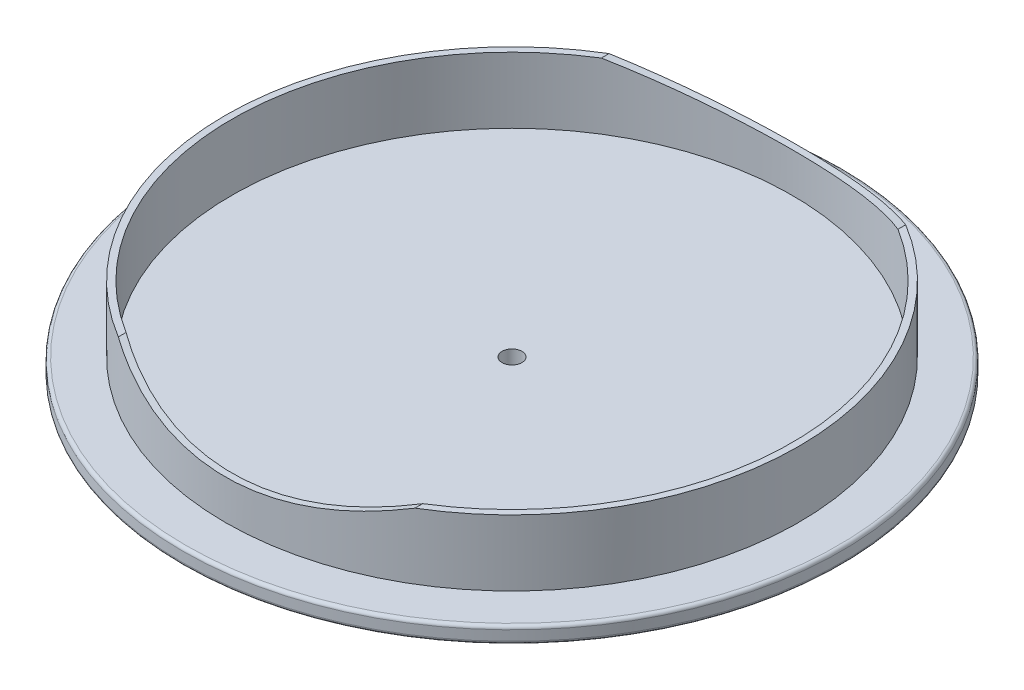
SolidWorks part; units mm, degrees
ref_plane "Front Plane" through (0, 0, 0) normal (0, 0, 1) x (1, 0, 0)
ref_plane "Top Plane" through (0, 0, 0) normal (0, 1, 0) x (1, 0, 0)
ref_plane "Right Plane" through (0, 0, 0) normal (1, 0, 0) x (0, 0, -1)
sketch "Sketch2" plane through (0, 0, 0) normal (0, 1, 0) x (1, 0, 0)
  circle A0 centre (0, 0) radius 100
  circle A3 centre (0, 0) radius 87
  circle A4 centre (0, 0) radius 85
  dimension "D1" = 170
  dimension "D2" = 174
  dimension "D3" = 200
extrude "Boss-Extrude1" add sketch "Sketch2" along normal blind 5 contours A0 A3 | A3 A4 | A4 region at (-97.1716, 0, 0) region at (-86.7539, 0, 0) region at (0, 0, 0)
extrude "Boss-Extrude2" add sketch "Sketch2<3>" along normal blind 25 contours A3 A4 region at (-86.7539, 0, 0)
sketch "Sketch2<3>" plane through (0, 0, 0) normal (0, 1, 0) x (1, 0, 0) same geometry as "Sketch2"
sketch "Sketch3" plane through (0, 0, 0) normal (0, 0, 1) x (1, 0, 0)
  line L0 (87, 25) -> (-87, 25) construction
  line L1 (0, 0) -> (0, 78.1705) construction
  line L2 (-45, 25) -> (-45, 27.804)
  line L3 (-45, 27.804) -> (45, 27.804)
  line L4 (45, 27.804) -> (45, 25)
  arc A0 (-45, 25) -> (45, 25) centre (0, 147.2936) ccw
  dimension "D1" = 90
extrude "Cut-Extrude1" cut sketch "Sketch3" against normal through all both and the other way through all
sketch "Sketch4" plane through (0, 0, 0) normal (0, -1, 0) x (1, 0, 0)
  circle A0 centre (0, 0) radius 3
  dimension "D1" = 6
extrude "Cut-Extrude2" cut sketch "Sketch4" against normal through all
fillet "Fillet1" radius 1 2 edges at (0, 0, 100) (0, 5, 100)
